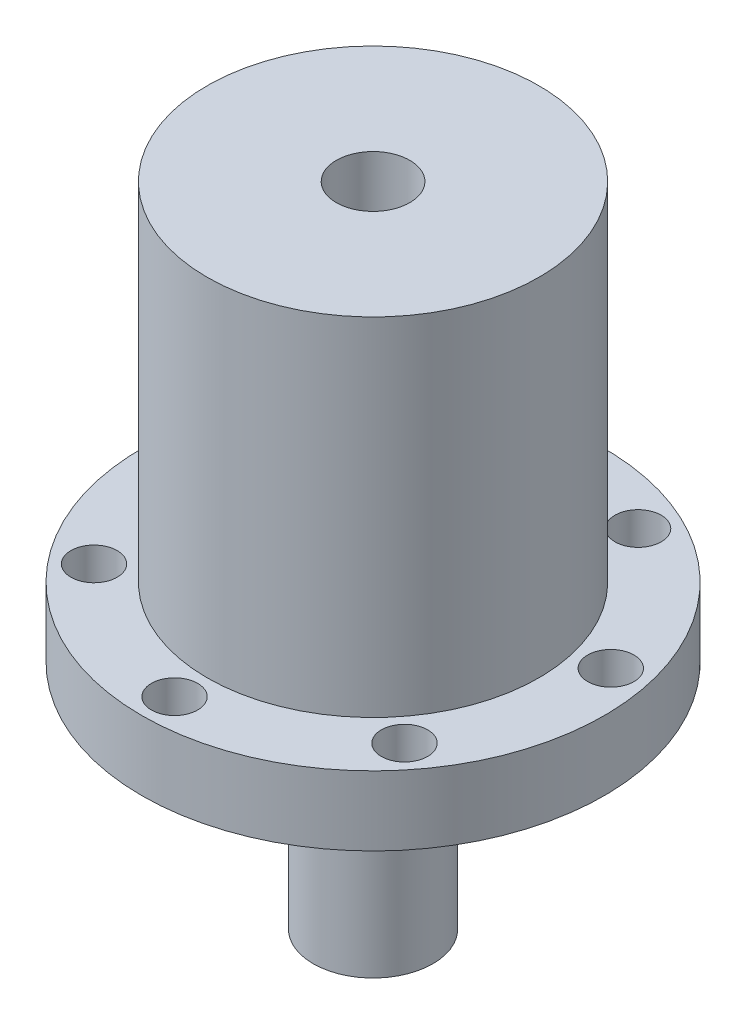
SolidWorks part; units mm, degrees
ref_plane "Front Plane" through (0, 0, 0) normal (0, 0, 1) x (1, 0, 0)
ref_plane "Top Plane" through (0, 0, 0) normal (0, 1, 0) x (1, 0, 0)
ref_plane "Right Plane" through (0, 0, 0) normal (1, 0, 0) x (0, 0, -1)
sketch "Sketch1" plane through (0, 0, 0) normal (0, 1, 0) x (1, 0, 0)
  circle A0 centre (0, 0) radius 1.5875
  circle A1 centre (0, 0) radius 7.175
  circle A2 centre (0, 0) radius 10
  point P25 (0, 0)
extrude "Boss-Extrude1" add sketch "Sketch1" along normal blind 15 and the other way blind 3 contours A1 A0 region at (-6.9721, 0, 0)
extrude "Boss-Extrude2" add sketch "Sketch1<3>" against normal blind 3 separate body contours A2 A1 region at (-9.7172, 0, 0)
sketch "Sketch1<3>" plane through (0, 0, 0) normal (0, 1, 0) x (1, 0, 0) same geometry as "Sketch1"
sketch "Sketch2" plane through (0, 0, 0) normal (1, 0, 0) x (0, 0, -1)
  circle A0 centre (0, 6.7029) radius 2.5
extrude "Cut-Extrude1" cut sketch "Sketch2" against normal blind 15
sketch "Sketch3" plane through (0, -3, 0) normal (0, -1, 0) x (1, 0, 0)
  circle A1 centre (0, 8.5849) radius 1
  circle A2 centre (6.712, 5.3526) radius 1
  circle A3 centre (8.3697, -1.9103) radius 1
  circle A4 centre (3.7249, -7.7348) radius 1
  circle A5 centre (-3.7249, -7.7348) radius 1
  circle A6 centre (-8.3697, -1.9103) radius 1
  circle A7 centre (-6.712, 5.3526) radius 1
  point P2 (0, 0)
  point P3 (0, 10.8219)
  point P14 (0, 0)
  point P18 (0, 8.5849)
  dimension "D1" = 7
extrude "Cut-Extrude2" cut sketch "Sketch3" against normal through all and the other way through all
sketch "Sketch4" plane through (0, -3, 0) normal (0, -1, 0) x (1, 0, 0)
  circle A0 centre (0, 0) radius 2.5875
extrude "Boss-Extrude4" add sketch "Sketch4" along normal blind 10 contours A0
extrude "Cut-Extrude3" cut sketch "Sketch1<5>" against normal blind 13 and the other way blind 15 contours A0
sketch "Sketch1<5>" plane through (0, 0, 0) normal (0, 1, 0) x (1, 0, 0) same geometry as "Sketch1"
